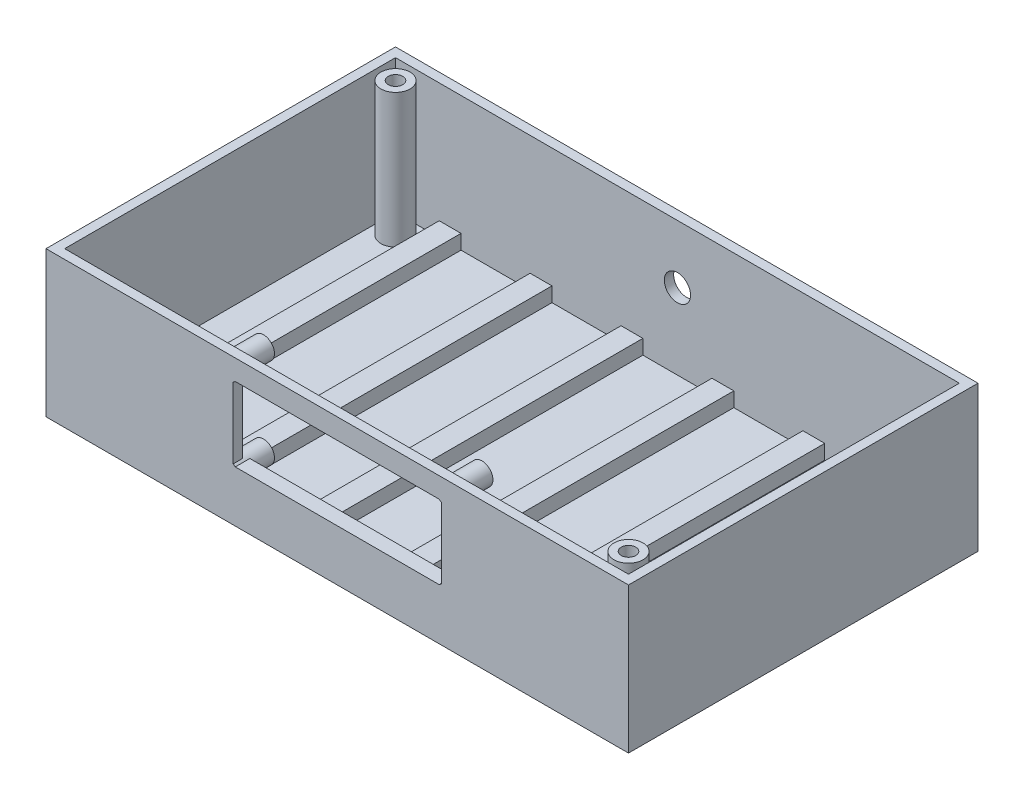
SolidWorks part; units mm, degrees
ref_plane "Alzado" through (0, 0, 0) normal (0, 0, 1) x (1, 0, 0)
ref_plane "Planta" through (0, 0, 0) normal (0, 1, 0) x (1, 0, 0)
ref_plane "Vista lateral" through (0, 0, 0) normal (1, 0, 0) x (0, 0, -1)
sketch "Croquis1" plane through (0, 0, 0) normal (0, 1, 0) x (1, 0, 0)
  line L1 (-100, 60) -> (100, 60)
  line L2 (-100, 60) -> (-100, -60)
  line L3 (-100, -60) -> (100, -60)
  line L4 (100, 60) -> (100, -60)
  line L5 (-100, 60) -> (100, -60) construction
  line L6 (-100, -60) -> (100, 60) construction
  point P0 (0, 0)
  dimension "D1" = 120
  dimension "D2" = 200
extrude "Saliente-Extruir1" add sketch "Croquis1" along normal blind 50
sketch "Croquis2" plane through (0, 50, 0) normal (0, 1, 0) x (1, 0, 0)
  line L1 (-96.8, 56.8) -> (96.8, 56.8)
  line L2 (-96.8, 56.8) -> (-96.8, -56.8)
  line L3 (-96.8, -56.8) -> (96.8, -56.8)
  line L4 (96.8, 56.8) -> (96.8, -56.8)
  line L5 (-96.8, 56.8) -> (96.8, -56.8) construction
  line L6 (-96.8, -56.8) -> (96.8, 56.8) construction
  point P0 (0, 0)
  dimension "D1" = 113.6
  dimension "D2" = 193.6
extrude "Cortar-Extruir1" cut sketch "Croquis2" against normal blind 46
sketch "Croquis3" plane through (0, 0, 60) normal (0, 0, 1) x (1, 0, 0)
  line L0 (-35.75, 50) -> (-35.75, 0) construction
  line L1 (-100, 50) -> (100, 50) construction
  line L2 (-100, 0) -> (100, 0) construction
  line L3 (35.75, 50) -> (35.75, 0) construction
  line L4 (-100, 50) -> (-100, 0) construction
  line L5 (100, 50) -> (100, 0) construction
  line L7 (-35.75, 43) -> (35.75, 43)
  line L8 (-35.75, 43) -> (-35.75, 17.6)
  line L9 (-35.75, 17.6) -> (35.75, 17.6)
  line L10 (35.75, 43) -> (35.75, 17.6)
  dimension "D1" = 64.25
  dimension "D2" = 64.25
  dimension "D3" = 25.4
  dimension "D4" = 7
extrude "Cortar-Extruir2" cut sketch "Croquis3" against normal blind 3.5
sketch "Croquis4" plane through (0, 0, 60) normal (0, 0, 1) x (1, 0, 0)
  line L1 (-37.5, 45.8) -> (37.5, 45.8) construction
  line L2 (-37.5, 45.8) -> (-37.5, 14.8) construction
  line L3 (-37.5, 14.8) -> (37.5, 14.8) construction
  line L4 (37.5, 45.8) -> (37.5, 14.8) construction
  line L5 (-37.5, 45.8) -> (37.5, 14.8) construction
  line L6 (-37.5, 14.8) -> (37.5, 45.8) construction
  line L8 (35.75, 17.6) -> (35.75, 43) construction
  line L9 (-35.75, 17.6) -> (35.75, 17.6) construction
  circle A0 centre (-37.5, 45.8) radius 3.75
  circle A1 centre (37.5, 45.8) radius 3.75
  circle A2 centre (37.5, 14.8) radius 3.75
  circle A3 centre (-37.5, 14.8) radius 3.75
  point P0 (0, 30.3)
  dimension "D5" = 7.5
  dimension "D1" = 31
  dimension "D2" = 2.8
  dimension "D3" = 1.75
  dimension "D4" = 75
extrude "Saliente-Extruir2" add sketch "Croquis4" against normal blind 12.2
sketch "Croquis5" plane through (0, 0, 60) normal (0, 0, 1) x (1, 0, 0)
  line L0 (-35.0055, 17.6) -> (35.0055, 17.6) construction
  line L1 (-35.75, 17.6) -> (35.75, 17.6)
  line L2 (-35.75, 17.6) -> (-35.75, 13.6)
  line L3 (-35.75, 13.6) -> (35.75, 13.6)
  line L4 (35.75, 17.6) -> (35.75, 13.6)
  line L5 (35.0055, 43) -> (-35.0055, 43) construction
  line L6 (-35.75, 43) -> (35.75, 43)
  line L7 (-35.75, 43) -> (-35.75, 47)
  line L8 (-35.75, 47) -> (35.75, 47)
  line L9 (35.75, 43) -> (35.75, 47)
  line L12 (35.75, 18.1166) -> (35.75, 42.4834) construction
  point P12 (35.75, 45)
  dimension "D1" = 4
  dimension "D2" = 4
  dimension "D3" = 71.5
  dimension "D4" = 71.5
  dimension "D5" = 0
  dimension "D6" = 0
extrude "Saliente-Extruir3" add sketch "Croquis5" against normal blind 5
sketch "Croquis6" plane through (0, 4, 0) normal (0, 1, 0) x (1, 0, 0)
  line L0 (96.8, 56.8) -> (-96.8, 56.8) construction
  line L1 (-81.8, 56.8) -> (-74.3, 56.8)
  line L2 (-81.8, 56.8) -> (-81.8, -56.8)
  line L3 (-81.8, -56.8) -> (-74.3, -56.8)
  line L4 (-74.3, 56.8) -> (-74.3, -56.8)
  line L5 (-96.8, -56.8) -> (96.8, -56.8) construction
  line L6 (-96.8, 56.8) -> (-96.8, -56.8) construction
  line L7 (-50.58, 56.8) -> (-50.58, -56.8)
  line L8 (-50.58, 56.8) -> (-43.08, 56.8)
  line L9 (-43.08, 56.8) -> (-43.08, -56.8)
  line L10 (-50.58, -56.8) -> (-43.08, -56.8)
  line L11 (-19.36, 56.8) -> (-19.36, -56.8)
  line L12 (-19.36, 56.8) -> (-11.86, 56.8)
  line L13 (-11.86, 56.8) -> (-11.86, -56.8)
  line L14 (-19.36, -56.8) -> (-11.86, -56.8)
  line L15 (11.86, 56.8) -> (11.86, -56.8)
  line L16 (11.86, 56.8) -> (19.36, 56.8)
  line L17 (19.36, 56.8) -> (19.36, -56.8)
  line L18 (11.86, -56.8) -> (19.36, -56.8)
  line L19 (43.08, 56.8) -> (43.08, -56.8)
  line L20 (43.08, 56.8) -> (50.58, 56.8)
  line L21 (50.58, 56.8) -> (50.58, -56.8)
  line L22 (43.08, -56.8) -> (50.58, -56.8)
  line L23 (74.3, 56.8) -> (74.3, -56.8)
  line L24 (74.3, 56.8) -> (81.8, 56.8)
  line L25 (81.8, 56.8) -> (81.8, -56.8)
  line L26 (74.3, -56.8) -> (81.8, -56.8)
  line L27 (96.8, -56.8) -> (96.8, 56.8) construction
  line L28 (-100, 60) -> (-100, -60) construction
  line L29 (100, 60) -> (-100, 60) construction
  line L30 (100, -60) -> (100, 60) construction
  line L31 (-100, -60) -> (100, -60) construction
  circle A0 centre (-90, 50) radius 5
  circle A1 centre (90, 50) radius 5
  circle A2 centre (90, -50) radius 5
  circle A3 centre (-90, -50) radius 5
  dimension "D5" = 10
  dimension "D1" = 7.5
  dimension "D2" = 15
  dimension "D4" = 15
  dimension "D6" = 10
  dimension "D7" = 10
  dimension "D8" = 10
  dimension "D9" = 10
  dimension "D10" = 10
  dimension "D11" = 10
  dimension "D12" = 10
  dimension "D13" = 10
  dimension "D3" = 6
extrude "Saliente-Extruir4" add sketch "Croquis6" along normal blind 5 and the other way blind 5 contours L2 L1 L4 L3 | L7 L10 L9 L8 | L11 L14 L13 L12 | L15 L18 L17 L16 | L19 L22 L21 L20 | L23 L26 L25 L24
sketch "Croquis7" plane through (0, 0, -60) normal (0, 0, -1) x (-1, 0, 0)
  line L0 (0, 50) -> (0, 0) construction
  line L1 (-100, 50) -> (100, 50) construction
  line L2 (-100, 0) -> (100, 0) construction
  circle A0 centre (0, 30) radius 4.5
  dimension "D2" = 9
  dimension "D1" = 0
  dimension "D3" = 20
extrude "Cortar-Extruir3" cut sketch "Croquis7" against normal blind 3.3
extrude "Saliente-Extruir5" add sketch "Croquis6<5>" along normal blind 46 contours A0 | A2 region at (-90, 4, -50) region at (90, 4, 50)
sketch "Croquis6<5>" plane through (0, 4, 0) normal (0, 1, 0) x (1, 0, 0) same geometry as "Croquis6"
extrude "Saliente-Extruir6" add sketch "Croquis6<6>" along normal blind 5 and the other way blind 5 contours A1 | A3 region at (90, 4, -50)
sketch "Croquis6<6>" plane through (0, 4, 0) normal (0, 1, 0) x (1, 0, 0) same geometry as "Croquis6"
sketch "Croquis8" plane through (0, 50, 0) normal (0, 1, 0) x (1, 0, 0)
  circle A0 centre (-90, 50) radius 2.5
  circle A1 centre (90, -50) radius 2.5
  dimension "D1" = 5
  dimension "D2" = 5
extrude "Cortar-Extruir4" cut sketch "Croquis8" against normal blind 20
sketch "Croquis9" plane through (0, 9, 0) normal (0, 1, 0) x (1, 0, 0)
  circle A0 centre (-90, -50) radius 2.5
  circle A1 centre (90, 50) radius 2.5
  dimension "D1" = 5
  dimension "D2" = 5
extrude "Cortar-Extruir5" cut sketch "Croquis9" against normal through all
